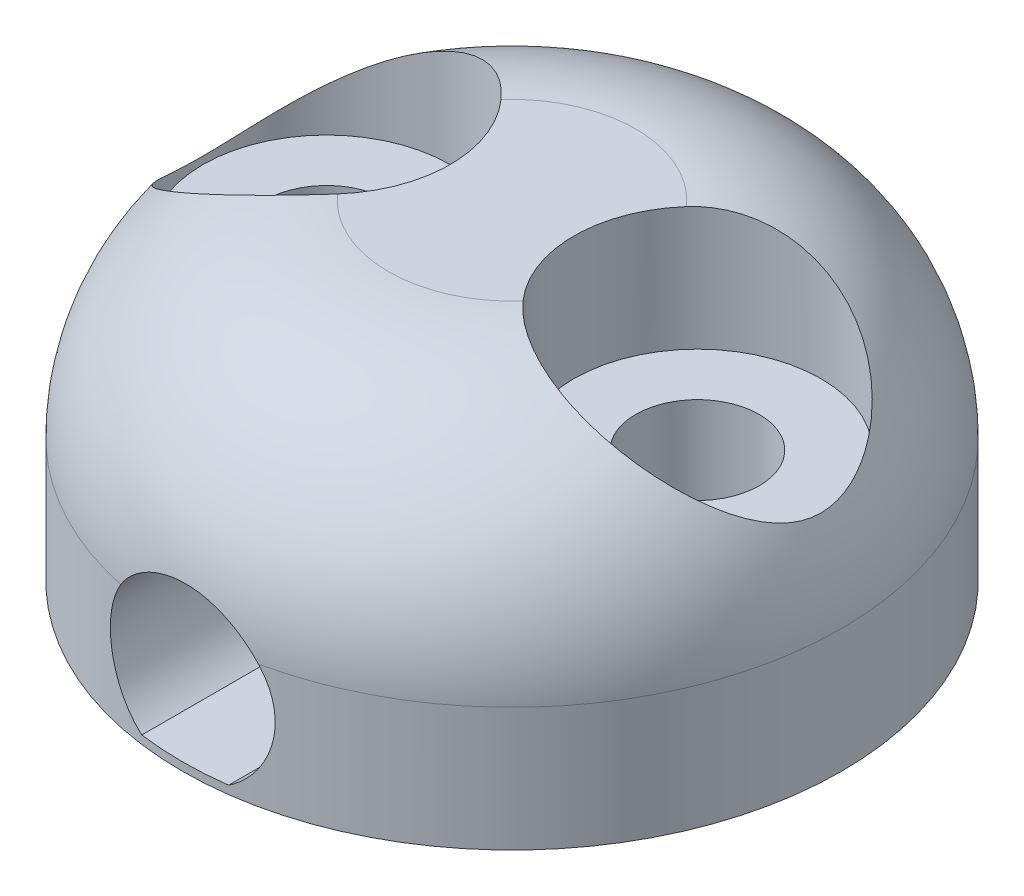
SolidWorks part; units mm, degrees
material "ABS"
ref_plane "Front" through (0, 0, 0) normal (0, 0, 1) x (1, 0, 0)
ref_plane "Top" through (0, 0, 0) normal (0, 1, 0) x (1, 0, 0)
ref_plane "Right" through (0, 0, 0) normal (1, 0, 0) x (0, 0, -1)
sketch "Esquisse1" plane through (0, 0, 0) normal (0, 1, 0) x (1, 0, 0)
  line L0 (0, -50) -> (0, 50) construction
  circle A0 centre (0, 0) radius 8
  circle A1 centre (-4.5, 0) radius 1.5
  circle A2 centre (4.5, 0) radius 1.5
  point P5 (0, 0)
  dimension "D1" = 16
  dimension "D2" = 3
  dimension "D3" = 9
extrude "Boss.-Extru.1" add sketch "Esquisse1" along normal blind 8
sketch "Esquisse2" plane through (0, 8, 0) normal (0, 1, 0) x (1, 0, 0)
  circle A0 centre (-4.5, 0) radius 3
  circle A1 centre (4.5, 0) radius 3
  circle A2 centre (-4.5, 0) radius 1.5 construction
  circle A3 centre (4.5, 0) radius 1.5 construction
  point P4 (0, 0)
  point P7 (0, 0)
  dimension "D1" = 6
extrude "Enlèv. mat.-Extru.1" cut sketch "Esquisse2" against normal blind 3
sketch "Esquisse3" plane through (0, 0, 0) normal (0, 0, 1) x (1, 0, 0)
  circle A0 centre (0, 1.9) radius 2
  point P2 (0, 0)
  dimension "D1" = 4
  dimension "D2" = 1.9
extrude "Enlèv. mat.-Extru.2" cut sketch "Esquisse3" against normal mid plane 40
fillet "Congé1" radius 5 1 edges at (0, 8, 8)
sketch "Esquisse4" plane through (0, 0, 0) normal (0, -1, 0) x (1, 0, 0)
  circle A0 centre (0, 0) radius 8
  arc A1 (-0.6245, 7.9756) -> (-0.6245, -7.9756) centre (0, 0) ccw construction
extrude "Boss.-Extru.2" add sketch "Esquisse4" against normal blind 0.2
